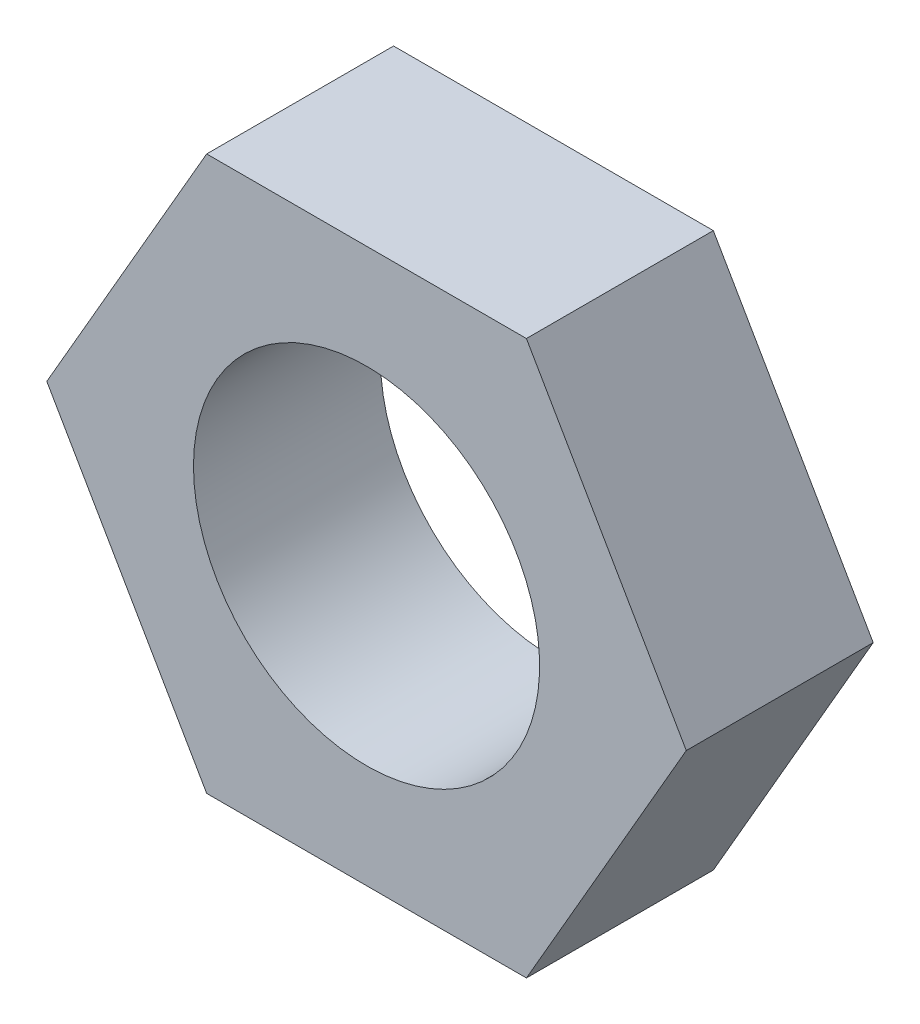
SolidWorks part; units mm, degrees
ref_plane "Front Plane" through (0, 0, 0) normal (0, 0, 1) x (1, 0, 0)
ref_plane "Top Plane" through (0, 0, 0) normal (0, 1, 0) x (1, 0, 0)
ref_plane "Right Plane" through (0, 0, 0) normal (1, 0, 0) x (0, 0, -1)
ref_plane "Plane1" through (0, 0, 2.7) normal (0, 0, 1) x (1, 0, 0)
sketch "Sketch1" plane through (0, 0, 2.7) normal (0, 0, 1) x (1, 0, 0)
  line L0 (-2.3094, 4) -> (-4.6188, 0)
  line L1 (-4.6188, 0) -> (-2.3094, -4)
  line L2 (-2.3094, -4) -> (2.3094, -4)
  line L3 (2.3094, -4) -> (4.6188, 0)
  line L4 (4.6188, 0) -> (2.3094, 4)
  line L5 (2.3094, 4) -> (-2.3094, 4)
  circle A0 centre (0, 0) radius 2.5
extrude "Boss-Extrude1" add sketch "Sketch1" against normal blind 2.7
ref_axis "Axis1" through (0, 0, -2.0403) along (0, 0, 1)
